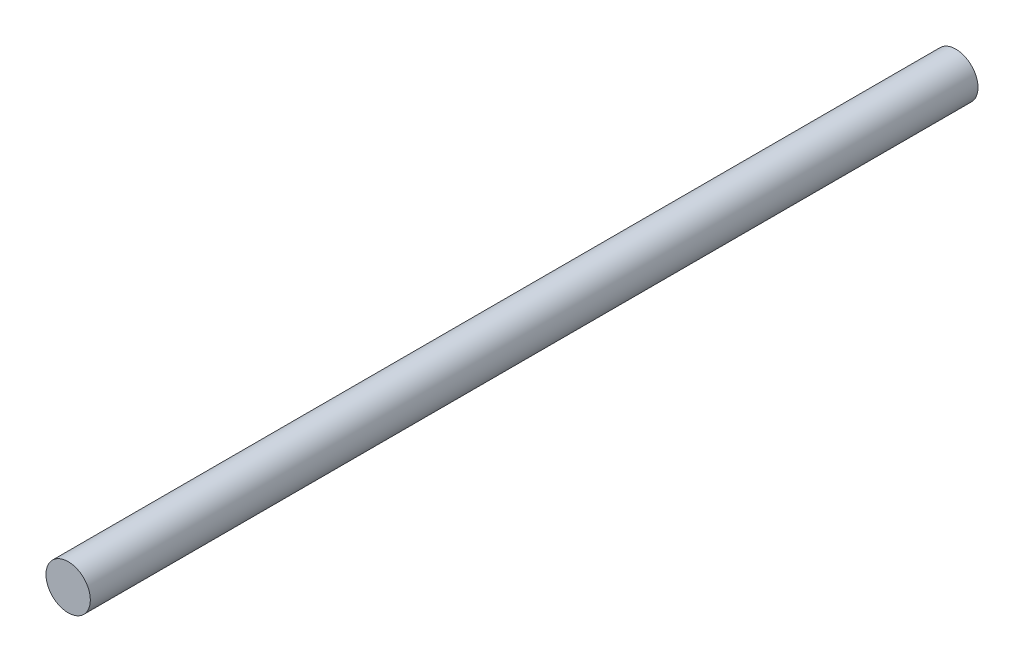
SolidWorks part; units mm, degrees
ref_plane "Front Plane" through (0, 0, 0) normal (0, 0, 1) x (1, 0, 0)
ref_plane "Top Plane" through (0, 0, 0) normal (0, 1, 0) x (1, 0, 0)
ref_plane "Right Plane" through (0, 0, 0) normal (1, 0, 0) x (0, 0, -1)
other "Default"
sketch "Sketch1" plane through (0, 0, 0) normal (0, 0, 1) x (1, 0, 0)
  circle A0 centre (0, 0) radius 4
  dimension "Diameter" = 8
extrude "Boss-Extrude1" add sketch "Sketch1" along normal mid plane 160
